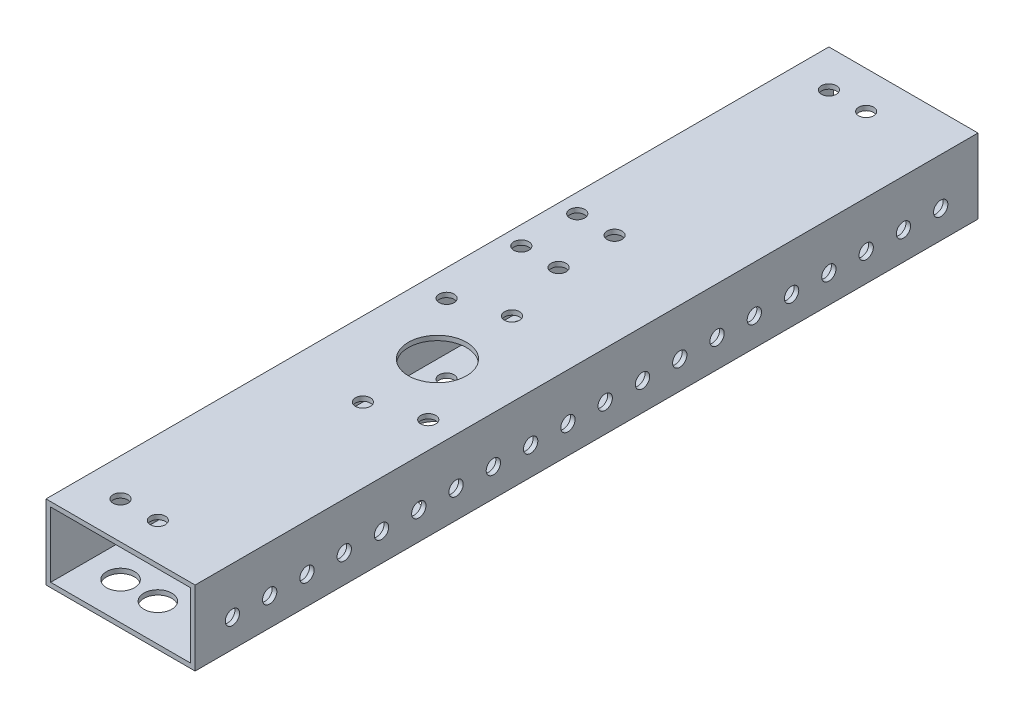
SolidWorks part; units mm, degrees
other "Markup1"
sketch "Sketch7" plane through (25.4, 12.7, -127) normal (0.9965, 0.0171, -0.0817) x (-0.082, 0.0128, -0.9966)
sketch "Sketch8" plane through (25.4, 12.7, -127) normal (0.9965, 0.0171, -0.0817) x (-0.082, 0.0128, -0.9966)
sketch "Sketch9" plane through (25.4, 12.7, -127) normal (0.9965, 0.0171, -0.0817) x (-0.082, 0.0128, -0.9966)
sketch "Sketch12" plane through (25.4, 12.7, -127) normal (0.9965, 0.0171, -0.0817) x (-0.082, 0.0128, -0.9966)
sketch "Sketch13" plane through (25.4, 12.7, -127) normal (0.9965, 0.0171, -0.0817) x (-0.082, 0.0128, -0.9966)
sketch "Sketch14" plane through (25.4, 12.7, -127) normal (0.9965, 0.0171, -0.0817) x (-0.082, 0.0128, -0.9966)
sketch "Sketch15" plane through (25.4, 12.7, -133.35) normal (0.9965, 0.0171, -0.0817) x (-0.082, 0.0128, -0.9966)
sketch "Sketch16" plane through (25.4, 12.7, -133.35) normal (0.9965, 0.0171, -0.0817) x (-0.082, 0.0128, -0.9966)
sketch "Sketch17" plane through (25.4, 12.7, -133.35) normal (0.9965, 0.0171, -0.0817) x (-0.082, 0.0128, -0.9966)
material "6061-T6 (SS)"
ref_plane "Front Plane" through (0, 0, 0) normal (0, 0, 1) x (1, 0, 0)
ref_plane "Top Plane" through (0, 0, 0) normal (0, 1, 0) x (1, 0, 0)
ref_plane "Right Plane" through (0, 0, 0) normal (1, 0, 0) x (0, 0, -1)
sketch "Sketch1" plane through (0, 0, 0) normal (0, 0, 1) x (1, 0, 0)
  line L0 (-23.8125, 11.1125) -> (23.8125, 11.1125)
  line L1 (-25.4, -12.7) -> (25.4, -12.7)
  line L2 (-25.4, -12.7) -> (-25.4, 12.7)
  line L3 (-25.4, 12.7) -> (25.4, 12.7)
  line L4 (25.4, -12.7) -> (25.4, 12.7)
  line L5 (-25.4, -12.7) -> (25.4, 12.7) construction
  line L6 (-25.4, 12.7) -> (25.4, -12.7) construction
  line L7 (23.8125, -11.1125) -> (23.8125, 11.1125)
  line L8 (-23.8125, -11.1125) -> (23.8125, -11.1125)
  line L9 (-23.8125, -11.1125) -> (-23.8125, 11.1125)
  point P0 (0, 0)
  dimension "D1" = 50.8
  dimension "D2" = 25.4
  dimension "D3" = 1.5875
extrude "Boss-Extrude1" add sketch "Sketch1" along normal mid plane 266.7
sketch "Sketch3" plane through (0, 12.7, 0) normal (0, 1, 0) x (1, 0, 0)
  line L0 (25.4, 133.35) -> (-25.4, 133.35) construction
  line L1 (25.4, -133.35) -> (-25.4, -133.35) construction
  line L3 (-25.4, -133.35) -> (-25.4, 133.35) construction
  line L4 (25.4, -133.35) -> (25.4, 133.35) construction
  circle A0 centre (-12.7, -120.65) radius 2.5527
  circle A1 centre (0, -120.65) radius 2.5527
  circle A2 centre (-12.7, 120.65) radius 2.5527
  circle A3 centre (0, 120.65) radius 2.5527
  dimension "D5" = 5.1054
  dimension "D1" = 12.7
  dimension "D2" = 12.7
  dimension "D3" = 12.7
  dimension "D4" = 12.7
  dimension "D6" = 12.7
  dimension "D7" = 12.7
  dimension "D8" = 12.7
  dimension "D9" = 25.4
  dimension "D10" = 12.7
  dimension "D11" = 25.4
extrude "Cut-Extrude1" cut sketch "Sketch3" against normal up to surface (1.5875 mm away) up to face at (0, 11.1125, 0)
sketch "Sketch5" plane through (0, -12.7, 0) normal (0, -1, 0) x (1, 0, 0)
  circle A0 centre (-12.7, -120.65) radius 2.5527 construction
  circle A1 centre (0, -120.65) radius 2.5527 construction
  circle A2 centre (0, 120.65) radius 2.5527 construction
  circle A3 centre (-12.7, 120.65) radius 2.5527 construction
  circle A4 centre (-12.7, -120.65) radius 2.5527
  circle A5 centre (0, -120.65) radius 2.5527
  circle A6 centre (0, 120.65) radius 2.5527
  circle A7 centre (-12.7, 120.65) radius 2.5527
  circle A8 centre (-12.7, 120.65) radius 4.7625
  circle A9 centre (0, 120.65) radius 4.7625
  circle A10 centre (0, -120.65) radius 4.7625
  circle A11 centre (-12.7, -120.65) radius 4.7625
  dimension "D1" = 9.525
extrude "Cut-Extrude2" cut sketch "Sketch5" against normal up to surface (1.5875 mm away) contours A10 A5 | A5 | A11 A4 | A4 | A6 | A9 A6 | A8 A7 | A7 region at (-12.7, -12.7, -120.65) region at (0, -12.7, -120.65) region at (0, -12.7, 120.65) region at (-12.7, -12.7, 120.65) region at (-17.3278, -12.7, 120.65) region at (-4.6278, -12.7, 120.65) region at (-4.6278, -12.7, -120.65) region at (-17.3278, -12.7, -120.65) up to face at (0, -11.1125, 0)
sketch "Sketch6" plane through (25.4, 0, 0) normal (1, 0, 0) x (0, 0, -1)
  line L0 (-133.35, -12.7) -> (-133.35, 12.7) construction
  line L1 (-133.35, -12.7) -> (133.35, -12.7) construction
  line L2 (0, 12.7) -> (0, -12.7) construction
  line L3 (-133.35, 12.7) -> (133.35, 12.7) construction
  circle A0 centre (-120.65, -3.175) radius 2.4384
  circle A19 centre (-107.95, -3.175) radius 2.4384
  circle A20 centre (-95.25, -3.175) radius 2.4384
  circle A21 centre (-82.55, -3.175) radius 2.4384
  circle A22 centre (-69.85, -3.175) radius 2.4384
  circle A23 centre (-57.15, -3.175) radius 2.4384
  circle A24 centre (-44.45, -3.175) radius 2.4384
  circle A25 centre (-31.75, -3.175) radius 2.4384
  circle A26 centre (-19.05, -3.175) radius 2.4384
  circle A27 centre (-6.35, -3.175) radius 2.4384
  circle A28 centre (6.35, -3.175) radius 2.4384
  circle A29 centre (19.05, -3.175) radius 2.4384
  circle A30 centre (31.75, -3.175) radius 2.4384
  circle A31 centre (44.45, -3.175) radius 2.4384
  circle A32 centre (57.15, -3.175) radius 2.4384
  circle A33 centre (69.85, -3.175) radius 2.4384
  circle A34 centre (82.55, -3.175) radius 2.4384
  circle A35 centre (95.25, -3.175) radius 2.4384
  circle A36 centre (107.95, -3.175) radius 2.4384
  circle A37 centre (120.65, -3.175) radius 2.4384
  dimension "D1" = 4.8768
  dimension "D5" = 12.7
  dimension "D2" = 12.7
  dimension "D3" = 9.525
  dimension "D4" = 20
extrude "Cut-Extrude3" cut sketch "Sketch6" against normal up to next contours A0 | A19 | A20 | A21 | A23 | A22 | A24 | A25 | A26 | A27 | A28 | A29 | A30 | A31 | A32 | A37 | A36 | A35 | A34 | A33 | A24 | A33 region at (25.4, -3.175, 120.65) region at (25.4, -3.175, 107.95) region at (25.4, -3.175, 95.25) region at (25.4, -3.175, 82.55) region at (25.4, -3.175, 69.85) region at (25.4, -3.175, 57.15) region at (25.4, -3.175, 44.45) region at (25.4, -3.175, 31.75) region at (25.4, -3.175, 19.05) region at (25.4, -3.175, 6.35) region at (25.4, -3.175, -6.35) region at (25.4, -3.175, -19.05) region at (25.4, -3.175, -31.75) region at (25.4, -3.175, -44.45) region at (25.4, -3.175, -57.15) region at (25.4, -3.175, -69.85) region at (25.4, -3.175, -82.55) region at (25.4, -3.175, -95.25) region at (25.4, -3.175, -107.95) region at (25.4, -3.175, -120.65)
sketch "Sketch11" plane through (0, 12.7, 0) normal (0, 1, 0) x (1, 0, 0)
  line L0 (-25.4, -133.35) -> (-25.4, 133.35) construction
  line L1 (-6.35, 41.275) -> (-6.35, 22.225) construction
  line L2 (0, 0) -> (0, -50.8) construction
  line L3 (25.4, 133.35) -> (-25.4, 133.35) construction
  line L5 (-19.05, 41.275) -> (-3.7973, 41.275) construction
  line L6 (-19.05, 41.275) -> (-19.05, 22.225) construction
  line L7 (-19.05, 22.225) -> (-3.7973, 22.225) construction
  line L9 (-19.05, 41.275) -> (-16.8611, 39.9616) construction
  line L10 (-19.05, 22.225) -> (-16.8611, 23.5384) construction
  line L13 (-19.05, -34.925) -> (-19.05, -15.875) construction
  line L14 (16.3268, -44.8575) -> (-16.3268, -5.9425) construction
  circle A0 centre (0, -25.4) radius 9.906
  circle A1 centre (0, 0) radius 2.5527
  circle A2 centre (0, -50.8) radius 2.5527
  circle A4 centre (-19.05, 22.225) radius 2.5527
  circle A5 centre (-19.05, 41.275) radius 2.5527
  circle A7 centre (-6.35, 22.225) radius 2.5527
  circle A8 centre (-6.35, 41.275) radius 2.5527
  circle A13 centre (-16.3268, -5.9425) radius 2.5527
  circle A14 centre (16.3268, -44.8575) radius 2.5527
  point P2 (0, -25.4)
  point P8 (-3.175, 31.75)
  point P24 (0, -25.4)
  point P32 (16.4958, -6.0855)
  point P33 (-16.8611, -6.2283)
  dimension "D1" = 19.812
  dimension "D3" = 5.1054
  dimension "D4" = 25.4
  dimension "D5" = 19.05
  dimension "D6" = 5.1054
  dimension "D7" = 12.7
  dimension "D10" = 40
  dimension "D2" = 25.4
  dimension "D8" = 101.6
  dimension "D9" = 6.35
  dimension "D11" = 19.05
  dimension "D12" = 22.225
  dimension "1" = 25.4
extrude "Cut-Extrude4" cut sketch "Sketch11" against normal through all
